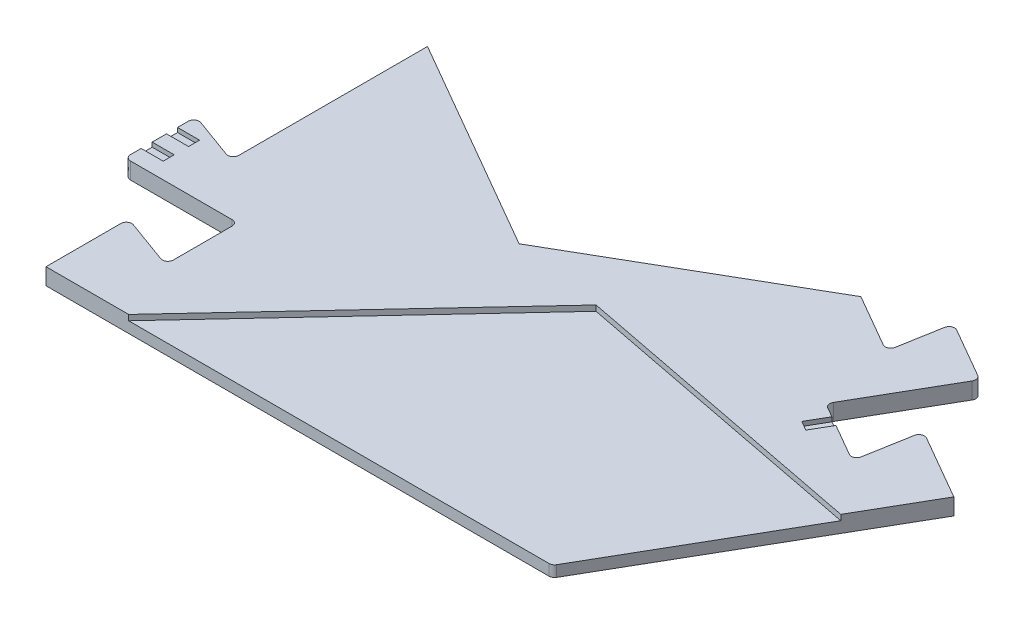
SolidWorks part; units mm, degrees
ref_plane "Přední rovina" through (0, 0, 0) normal (0, 0, 1) x (1, 0, 0)
ref_plane "Horní rovina" through (0, 0, 0) normal (0, 1, 0) x (1, 0, 0)
ref_plane "Pravá rovina" through (0, 0, 0) normal (1, 0, 0) x (0, 0, -1)
sketch "Skica1" plane through (0, 0, 0) normal (0, 1, 0) x (1, 0, 0)
  line L0 (105.5337, 53.6901) -> (118.5241, 46.1901)
  line L1 (118.5241, 46.1901) -> (91.8562, 0)
  line L2 (15, 0) -> (55.9106, 43.8899)
  line L3 (0, 0) -> (0, 15)
  line L4 (0, 15) -> (10.5, 11.1783)
  line L5 (10.5, 11.1783) -> (10.5, 24.2783)
  line L6 (10.5, 24.2783) -> (-9.9505, 24.2783)
  line L7 (55.9106, 43.8899) -> (111.0185, 33.1901)
  line L8 (0, 0) -> (91.8562, 0)
  line L9 (0, 33.5566) -> (-9.9505, 37.1783)
  line L10 (-9.9505, 37.1783) -> (-9.9505, 24.2783)
  line L11 (0, 69.22) -> (0, 33.5566)
  line L12 (0, 69.22) -> (39.3176, 46.52)
  line L13 (39.3176, 46.52) -> (78.6351, 69.22)
  line L14 (105.5337, 53.6901) -> (103.5934, 42.686)
  line L15 (103.5934, 42.686) -> (92.2485, 49.236)
  line L16 (78.6351, 69.22) -> (89.4632, 62.9684)
  line L17 (92.2485, 49.236) -> (102.4737, 66.9466)
  line L18 (89.4632, 62.9684) -> (91.302, 73.3966)
  line L19 (91.302, 73.3966) -> (102.4737, 66.9466)
  line L20 (0, 69.22) -> (0, 0) construction
  line L21 (78.6351, 69.22) -> (118.5241, 46.1901) construction
  point P0 (94.9308, 5.3253)
  dimension "D1" = 90
  dimension "D2" = 15
  dimension "D3" = 91.8562
  dimension "D4" = 70
  dimension "D5" = 15
  dimension "D6" = 122
  dimension "D7" = 69.22
  dimension "D8" = 60
  dimension "D9" = 13
  dimension "D10" = 120
  dimension "D11" = 45.4
  dimension "D12" = 45.4
  dimension "D13" = 69.22
  dimension "D14" = 70
  dimension "D15" = 70
  dimension "D16" = 120
  dimension "D17" = 120
  dimension "D18" = 13.1
  dimension "D19" = 12.9
  dimension "D20" = 10.5
  dimension "D21" = 12.9
  dimension "D22" = 13.1
  dimension "D23" = 10.5
  dimension "D24" = 15
extrude "Přidat vysunutím1" add sketch "Skica1" along normal blind 3 contours L19 L18 L16 L13 L12 L11 L9 L10 L6 L5 L4 L3 L8 L2 L7 L1 L0 L14 L15 L17 region at (43.6515, 0, -40.5739)
extrude "Přidat vysunutím2" add sketch "Skica1<3>" along normal blind 2 contours L2 L8 L1 L7 region at (66.2955, 0, -18.7917)
sketch "Skica1<3>" plane through (0, 0, 0) normal (0, 1, 0) x (1, 0, 0) same geometry as "Skica1"
fillet "Zaoblit1" radius 1 12 edges at (0, 1.5, -33.5566) (-9.9505, 1.5, -37.1783) (10.5, 1.5, -24.2783) (-9.9505, 1.5, -24.2783) (10.5, 1.5, -11.1783) (0, 1.5, -15) (105.5337, 1.5, -53.6901) (103.5934, 1.5, -42.686) (92.2485, 1.5, -49.236) (89.4632, 1.5, -62.9684) (91.302, 1.5, -73.3966) (102.4737, 1.5, -66.9466)
fillet "Zaoblit2" radius 1 1 edges at (91.8562, 1, 0)
sketch "Skica2" plane through (0, 3, 0) normal (0, 1, 0) x (1, 0, 0)
  line L0 (-9.9505, 33.8142) -> (-5.9505, 33.8142)
  line L1 (-5.9505, 33.8142) -> (-5.9505, 31.8142)
  line L2 (-5.9505, 31.8142) -> (-9.9505, 31.8142)
  line L3 (-9.9505, 30.5142) -> (39.5766, 30.5142) construction
  line L4 (-9.9505, 27.2142) -> (-5.9505, 27.2142)
  line L5 (-5.9505, 27.2142) -> (-5.9505, 29.2142)
  line L6 (-5.9505, 29.2142) -> (-9.9505, 29.2142)
  line L7 (-9.9505, 33.8142) -> (-9.9505, 31.8142)
  line L8 (-9.9505, 29.2142) -> (-9.9505, 27.2142)
  line L9 (-9.9505, 35.7502) -> (-9.9505, 25.2783) construction
  line L16 (92.7485, 50.102) -> (101.9737, 66.0806) construction
  line L17 (97.7355, 46.068) -> (68.7503, -4.1359) construction
  line L22 (102.3566, 43.4) -> (93.1145, 48.736) construction
  line L23 (94.8777, 47.718) -> (96.6097, 46.718)
  line L24 (92.8777, 44.2539) -> (94.8777, 47.718)
  line L25 (94.6097, 43.2539) -> (92.8777, 44.2539)
  line L26 (96.6097, 46.718) -> (94.6097, 43.2539)
  point P10 (-9.9505, 30.5142)
  point P11 (0, 0)
  point P14 (0, 0)
  point P29 (0, 0)
  point P33 (97.7355, 46.068)
  point P34 (97.7355, 46.068)
  dimension "D1" = 2
  dimension "D2" = 4
  dimension "D3" = 2.6
  dimension "D7" = 2
  dimension "D8" = 4
  dimension "D9" = 1.3
extrude "Odebrat vysunutím1" cut sketch "Skica2" against normal blind 0.8
